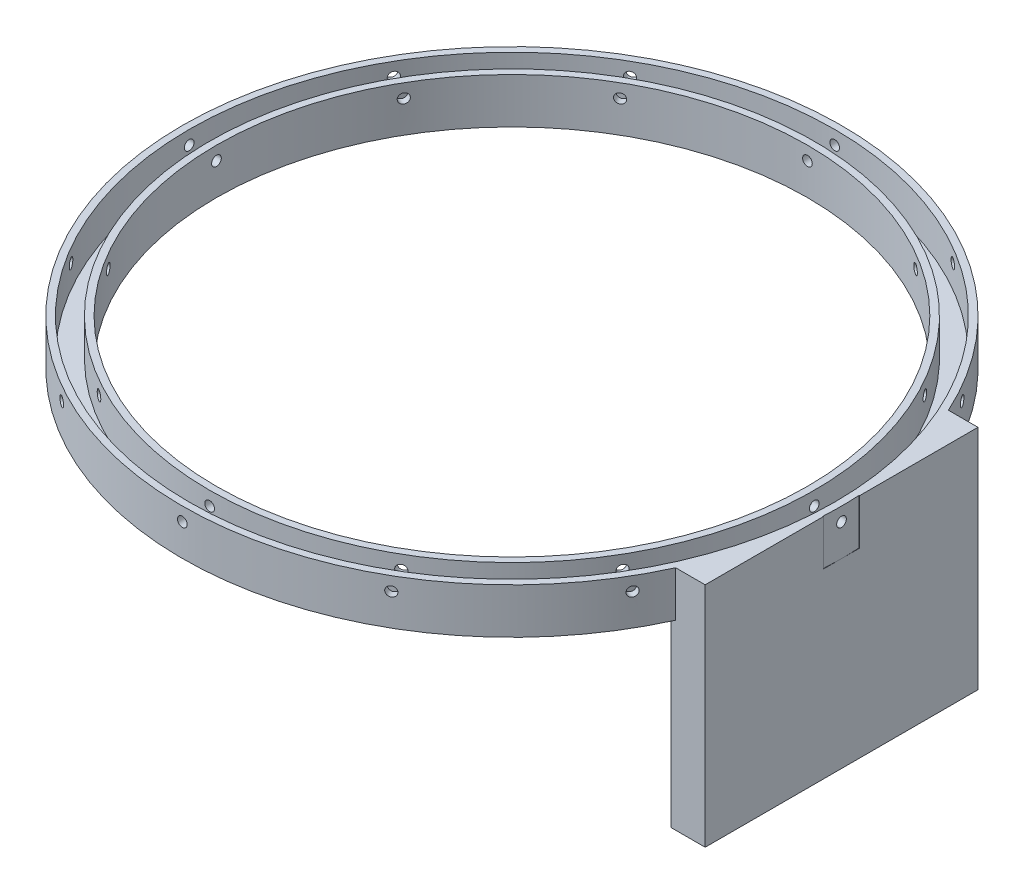
SolidWorks part; units mm, degrees
ref_plane "Front Plane" through (0, 0, 0) normal (0, 0, 1) x (1, 0, 0)
ref_plane "Top Plane" through (0, 0, 0) normal (0, 1, 0) x (1, 0, 0)
ref_plane "Right Plane" through (0, 0, 0) normal (1, 0, 0) x (0, 0, -1)
sketch "Sketch1" plane through (0, 0, 0) normal (0, 1, 0) x (1, 0, 0)
  circle A0 centre (0, 0) radius 92.075
  circle A1 centre (0, 0) radius 82.55
  dimension "D1" = 184.15
  dimension "D2" = 165.1
extrude "Boss-Extrude1" add sketch "Sketch1" along normal blind 12.7
sketch "Sketch2" plane through (0, 12.7, 0) normal (0, 1, 0) x (1, 0, 0)
  circle A0 centre (0, 0) radius 84.455
  circle A1 centre (0, 0) radius 90.17
  dimension "D1" = 180.34
  dimension "D2" = 168.91
extrude "Cut-Extrude1" cut sketch "Sketch2" against normal blind 10.16
sketch "Sketch3" plane through (0, 0, 0) normal (0, 0, 1) x (1, 0, 0)
  line L0 (92.075, 12.7) -> (-92.075, 12.7) construction
  circle A0 centre (0, 8.89) radius 1.3525
  dimension "D1" = 2.7051
  dimension "D2" = 3.81
extrude "Cut-Extrude2" cut sketch "Sketch3" against normal up to surface (92.0651 mm away) up to face at (0, 12.7, 92.075)
pattern_circular "CirPattern1" count 12 over 360 about axis through (0, 12.7, 0) along (0, 1, 0) of "Cut-Extrude2"
sketch "Sketch4" plane through (0, 0, 0) normal (0, -1, 0) x (-1, 0, 0)
  line L0 (0, 0) -> (-92.075, 0) construction
  line L1 (-92.075, 38.1) -> (-82.55, 38.1)
  line L2 (-92.075, 38.1) -> (-92.075, -38.1)
  line L3 (-92.075, -38.1) -> (-82.55, -38.1)
  line L4 (-82.55, 38.1) -> (-82.55, -38.1)
  circle A0 centre (0, 0) radius 82.55 construction
  circle A1 centre (0, 0) radius 92.075 construction
  point P10 (0, 0)
  dimension "D1" = 38.1
  dimension "D2" = 76.2
extrude "Boss-Extrude2" add sketch "Sketch4" along normal blind 50.8
sketch "Sketch5" plane through (0, 0, 0) normal (0, 1, 0) x (1, 0, 0)
  line L0 (92.075, -5.08) -> (91.9348, -5.08)
  line L1 (92.075, 5.08) -> (91.9348, 5.08)
  line L2 (92.075, 0) -> (92.075, 38.1)
  line L3 (92.075, 38.1) -> (83.8224, 38.1)
  line L4 (92.075, 5.08) -> (92.075, 38.1)
  line L5 (92.075, 38.1) -> (83.8224, 38.1)
  line L6 (83.8224, -38.1) -> (92.075, -38.1)
  line L7 (92.075, -38.1) -> (92.075, 0)
  line L8 (83.8224, -38.1) -> (92.075, -38.1)
  line L9 (92.075, -38.1) -> (92.075, -5.08)
  arc A1 (92.075, 0) -> (83.8224, 38.1) centre (0, 0) ccw
  arc A2 (91.9348, 5.08) -> (83.8224, 38.1) centre (0, 0) ccw
  arc A3 (83.8224, -38.1) -> (92.075, 0) centre (0, 0) ccw
  arc A4 (83.8224, -38.1) -> (91.9348, -5.08) centre (0, 0) ccw
  dimension "D3" = 5.08
  dimension "D4" = 5.08
  dimension "D1" = 0
  dimension "D2" = 0
extrude "Boss-Extrude4" add sketch "Sketch5" along normal up to surface (12.7 mm away) up to face at (0, 12.7, 90.17)
